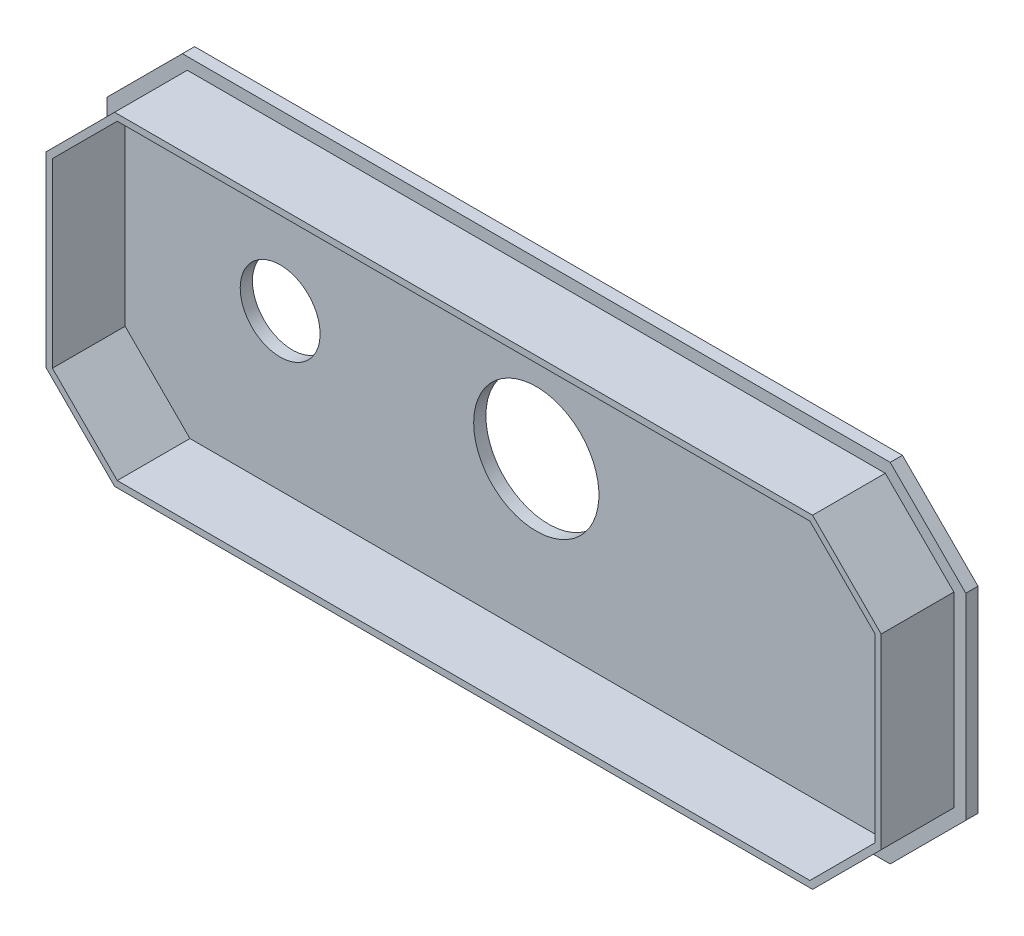
SolidWorks part; units mm, degrees
ref_plane "Front Plane" through (0, 0, 0) normal (0, 0, 1) x (1, 0, 0)
ref_plane "Top Plane" through (0, 0, 0) normal (0, 1, 0) x (1, 0, 0)
ref_plane "Right Plane" through (0, 0, 0) normal (1, 0, 0) x (0, 0, -1)
sketch "Sketch1" plane through (0, 0, 0) normal (0, 0, 1) x (1, 0, 0)
  line L1 (-28.1304, -11.3918) -> (28.1304, -11.3918)
  line L2 (-28.1304, -11.3918) -> (-28.1304, 11.3918)
  line L3 (-28.1304, 11.3918) -> (28.1304, 11.3918)
  line L4 (28.1304, -11.3918) -> (28.1304, 11.3918)
  line L5 (-28.1304, -11.3918) -> (28.1304, 11.3918) construction
  line L6 (-28.1304, 11.3918) -> (28.1304, -11.3918) construction
  point P0 (0, 0)
  dimension "D1" = 56.2608
  dimension "D2" = 22.7836
extrude "Boss-Extrude1" add sketch "Sketch1" along normal blind 0.8
sketch "Sketch2" plane through (0, 0, 0.8) normal (0, 0, 1) x (1, 0, 0)
  line L0 (-28.1304, -6.4421) -> (-23.1807, -11.3918)
  line L1 (-28.1304, 11.3918) -> (-28.1304, -11.3918) construction
  line L2 (-28.1304, 6.4421) -> (-23.1807, 11.3918)
  line L3 (28.1304, 11.3918) -> (-28.1304, 11.3918) construction
  line L4 (-23.1807, 11.3918) -> (-28.1304, 11.3918)
  line L5 (-28.1304, 11.3918) -> (-28.1304, 6.4421)
  line L6 (-28.1304, -11.3918) -> (28.1304, -11.3918) construction
  line L7 (-23.1807, -11.3918) -> (-28.1304, -11.3918)
  line L8 (-28.1304, -11.3918) -> (-28.1304, -6.4421)
  line L9 (23.1807, -11.3918) -> (28.1304, -6.4421)
  line L10 (28.1304, -11.3918) -> (28.1304, 11.3918) construction
  line L11 (28.1304, -6.4421) -> (28.1304, -11.3918)
  line L12 (28.1304, -11.3918) -> (23.1807, -11.3918)
  line L13 (23.1807, 11.3918) -> (28.1304, 6.4421)
  line L14 (28.1304, 6.4421) -> (28.1304, 11.3918)
  line L15 (28.1304, 11.3918) -> (23.1807, 11.3918)
  dimension "D1" = 7
  dimension "D2" = 7
  dimension "D3" = 7
  dimension "D4" = 7
  dimension "D5" = 45
  dimension "D6" = 45
  dimension "D7" = 45
  dimension "D8" = 45
extrude "Cut-Extrude1" cut sketch "Sketch2" against normal through all
sketch "Sketch3" plane through (0, 0, 0.8) normal (0, 0, 1) x (1, 0, 0)
  line L0 (22.8576, 10.6118) -> (-22.8576, 10.6118)
  line L1 (-22.8576, 10.6118) -> (-27.3504, 6.119)
  line L2 (-27.3504, 6.119) -> (-27.3504, -6.119)
  line L3 (-27.3504, -6.119) -> (-22.8576, -10.6118)
  line L4 (-22.8576, -10.6118) -> (22.8576, -10.6118)
  line L5 (22.8576, -10.6118) -> (27.3504, -6.119)
  line L6 (27.3504, -6.119) -> (27.3504, 6.119)
  line L7 (27.3504, 6.119) -> (22.8576, 10.6118)
  line L48 (-22.6836, 10.1918) -> (-26.9304, 5.945)
  line L49 (-26.9304, 5.945) -> (-26.9304, -5.945)
  line L50 (-26.9304, -5.945) -> (-22.6836, -10.1918)
  line L51 (-22.6836, -10.1918) -> (22.6836, -10.1918)
  line L52 (22.6836, -10.1918) -> (26.9304, -5.945)
  line L53 (26.9304, -5.945) -> (26.9304, 5.945)
  line L54 (26.9304, 5.945) -> (22.6836, 10.1918)
  line L55 (22.6836, 10.1918) -> (-22.6836, 10.1918)
  line L56 (-22.6836, 10.1918) -> (-26.9304, 5.945)
  line L57 (-26.9304, 5.945) -> (-26.9304, -5.945)
  line L58 (-26.9304, -5.945) -> (-22.6836, -10.1918)
  line L59 (-22.6836, -10.1918) -> (22.6836, -10.1918)
  line L60 (22.6836, -10.1918) -> (26.9304, -5.945)
  line L61 (26.9304, -5.945) -> (26.9304, 5.945)
  line L62 (26.9304, 5.945) -> (22.6836, 10.1918)
  line L63 (22.6836, 10.1918) -> (-22.6836, 10.1918)
  dimension "D1" = 1.2
  dimension "D2" = 0.42
extrude "Boss-Extrude2" add sketch "Sketch3" along normal blind 4.7625
sketch "Sketch4" plane through (0, 0, 0) normal (0, 0, -1) x (-1, 0, 0)
  line L0 (16.7766, 0) -> (0, 0) construction
  line L1 (28.1304, 6.4421) -> (28.1304, -6.4421) construction
  circle A0 centre (16.7766, 0) radius 2.6162
  dimension "D1" = 5.2324
  dimension "D2" = 11.3538
extrude "Cut-Extrude2" cut sketch "Sketch4" against normal blind 2.54
sketch "Sketch5" plane through (0, 0, 0) normal (0, 0, -1) x (-1, 0, 0)
  circle A0 centre (0, 0) radius 4.1021
  dimension "D1" = 8.2042
extrude "Cut-Extrude3" cut sketch "Sketch5" against normal blind 2.54
